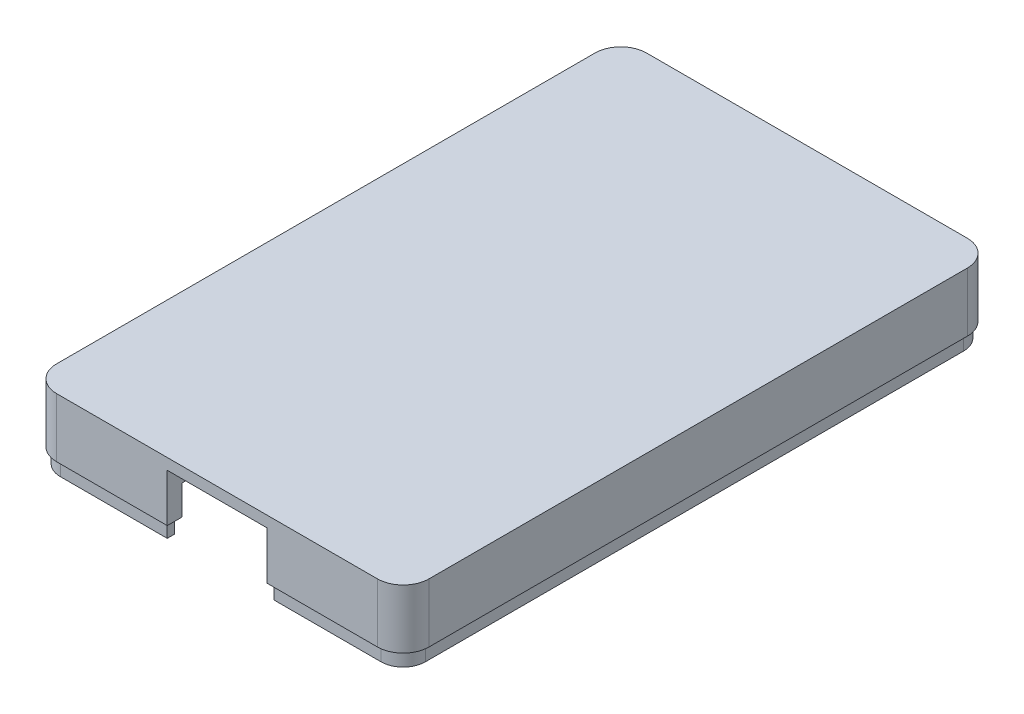
SolidWorks part; units mm, degrees
ref_plane "Alzado" through (0, 0, 0) normal (0, 0, 1) x (1, 0, 0)
ref_plane "Planta" through (0, 0, 0) normal (0, 1, 0) x (1, 0, 0)
ref_plane "Vista lateral" through (0, 0, 0) normal (1, 0, 0) x (0, 0, -1)
sketch "Sketch1" plane through (0, 0, 0) normal (0, 1, 0) x (1, 0, 0)
  line L1 (-21.75, -40) -> (21.75, -40)
  line L2 (-25.25, -36.5) -> (-25.25, 36.5)
  line L3 (-21.75, 40) -> (21.75, 40)
  line L4 (25.25, -36.5) -> (25.25, 36.5)
  line L5 (-25.25, -40) -> (25.25, 40) construction
  line L6 (-25.25, 40) -> (25.25, -40) construction
  arc A0 (-21.75, -40) -> (-25.25, -36.5) centre (-21.75, -36.5) cw
  arc A1 (21.75, -40) -> (25.25, -36.5) centre (21.75, -36.5) ccw
  arc A2 (-25.25, 36.5) -> (-21.75, 40) centre (-21.75, 36.5) cw
  arc A3 (21.75, 40) -> (25.25, 36.5) centre (21.75, 36.5) cw
  point P0 (0, 0)
  dimension "D3" = 3.5
  dimension "D1" = 50.5
  dimension "D2" = 80
extrude "Boss-Extrude1" add sketch "Sketch1" along normal blind 8
sketch "Sketch2" plane through (0, 0, 0) normal (0, -1, 0) x (1, 0, 0)
  line L0 (25.25, 36.5) -> (25.25, -36.5) construction
  line L1 (-19.75, -38) -> (19.75, -38)
  line L2 (-23.25, -34.5) -> (-23.25, 34.5)
  line L3 (-19.75, 38) -> (19.75, 38)
  line L4 (23.25, -34.5) -> (23.25, 34.5)
  line L5 (-23.25, -38) -> (23.25, 38) construction
  line L6 (-23.25, 38) -> (23.25, -38) construction
  line L7 (-21.75, 40) -> (21.75, 40) construction
  arc A0 (19.75, -38) -> (23.25, -34.5) centre (19.75, -34.5) ccw
  arc A1 (-19.75, -38) -> (-23.25, -34.5) centre (-19.75, -34.5) cw
  arc A2 (-23.25, 34.5) -> (-19.75, 38) centre (-19.75, 34.5) cw
  arc A3 (19.75, 38) -> (23.25, 34.5) centre (19.75, 34.5) cw
  point P0 (0, 0)
  dimension "D3" = 3.5
  dimension "D1" = 2
  dimension "D2" = 2
extrude "Cut-Extrude1" cut sketch "Sketch2" against normal blind 4
sketch "Sketch3" plane through (0, 0, 40) normal (0, 0, 1) x (1, 0, 0)
  line L0 (0, 0) -> (0, 8) construction
  line L1 (-21.75, 8) -> (21.75, 8) construction
  line L3 (-6.75, 6.5) -> (6.75, 6.5)
  line L4 (-6.75, 6.5) -> (-6.75, -6.5)
  line L5 (-6.75, -6.5) -> (6.75, -6.5)
  line L6 (6.75, 6.5) -> (6.75, -6.5)
  line L7 (-6.75, 6.5) -> (6.75, -6.5) construction
  line L8 (-6.75, -6.5) -> (6.75, 6.5) construction
  dimension "D1" = 1.5
  dimension "D2" = 13.5
extrude "Cut-Extrude2" cut sketch "Sketch3" against normal blind 15
curve "CurvaComp1"
curve "CurvaComp2"
sketch "Croquis2" plane through (0, 0, 0) normal (0, -1, 0) x (1, 0, 0)
  line L0 (-6.75, 40) -> (-6.75, 38) construction
  line L1 (-6.75, 40) -> (-6.75, 38)
  line L4 (-21.75, 40) -> (-6.75, 40) construction
  line L5 (-25.25, -36.5) -> (-25.25, 36.5) construction
  line L6 (21.75, -40) -> (-21.75, -40) construction
  line L7 (25.25, 36.5) -> (25.25, -36.5) construction
  line L8 (6.75, 40) -> (21.75, 40) construction
  line L9 (-21.75, 40) -> (-6.75, 40)
  line L10 (-25.25, -36.5) -> (-25.25, 36.5)
  line L11 (21.75, -40) -> (-21.75, -40)
  line L12 (25.25, 36.5) -> (25.25, -36.5)
  line L13 (6.75, 40) -> (21.75, 40)
  line L14 (-19.75, 38) -> (-6.75, 38) construction
  line L15 (-23.25, -34.5) -> (-23.25, 34.5) construction
  line L16 (19.75, -38) -> (-19.75, -38) construction
  line L17 (23.25, 34.5) -> (23.25, -34.5) construction
  line L19 (-19.75, 38) -> (-6.75, 38)
  line L20 (-23.25, -34.5) -> (-23.25, 34.5)
  line L21 (19.75, -38) -> (-19.75, -38)
  line L22 (23.25, 34.5) -> (23.25, -34.5)
  line L24 (6.75, 38) -> (6.75, 40) construction
  line L25 (6.75, 38) -> (6.75, 40)
  line L26 (19.75, 38) -> (6.75, 38) construction
  line L27 (19.75, 38) -> (6.75, 38)
  arc A0 (-21.75, 40) -> (-25.25, 36.5) centre (-21.75, 36.5) ccw construction
  arc A1 (-25.25, -36.5) -> (-21.75, -40) centre (-21.75, -36.5) ccw construction
  arc A2 (21.75, -40) -> (25.25, -36.5) centre (21.75, -36.5) ccw construction
  arc A3 (25.25, 36.5) -> (21.75, 40) centre (21.75, 36.5) ccw construction
  arc A4 (-21.75, 40) -> (-25.25, 36.5) centre (-21.75, 36.5) ccw
  arc A5 (-25.25, -36.5) -> (-21.75, -40) centre (-21.75, -36.5) ccw
  arc A6 (21.75, -40) -> (25.25, -36.5) centre (21.75, -36.5) ccw
  arc A7 (25.25, 36.5) -> (21.75, 40) centre (21.75, 36.5) ccw
  arc A8 (-19.75, 38) -> (-23.25, 34.5) centre (-19.75, 34.5) ccw construction
  arc A9 (-23.25, -34.5) -> (-19.75, -38) centre (-19.75, -34.5) ccw construction
  arc A10 (19.75, -38) -> (23.25, -34.5) centre (19.75, -34.5) ccw construction
  arc A11 (23.25, 34.5) -> (19.75, 38) centre (19.75, 34.5) ccw construction
  arc A12 (-19.75, 38) -> (-23.25, 34.5) centre (-19.75, 34.5) ccw
  arc A13 (-23.25, -34.5) -> (-19.75, -38) centre (-19.75, -34.5) ccw
  arc A14 (19.75, -38) -> (23.25, -34.5) centre (19.75, -34.5) ccw
  arc A15 (23.25, 34.5) -> (19.75, 38) centre (19.75, 34.5) ccw
sketch "Croquis3" plane through (0, 0, 0) normal (0, -1, 0) x (1, 0, 0)
  line L12 (7.25, 38.5) -> (19.75, 38.5)
  line L13 (7.25, 38.5) -> (19.75, 38.5)
  line L14 (7.25, 39.5) -> (7.25, 38.5)
  line L15 (7.25, 39.5) -> (7.25, 38.5)
  line L24 (-24.75, 36.5) -> (-24.75, -36.5)
  line L25 (-7.25, 39.5) -> (-21.75, 39.5)
  line L26 (-7.25, 38.5) -> (-7.25, 39.5)
  line L27 (-19.75, 38.5) -> (-7.25, 38.5)
  line L28 (-23.75, -34.5) -> (-23.75, 34.5)
  line L29 (19.75, -38.5) -> (-19.75, -38.5)
  line L30 (23.75, 34.5) -> (23.75, -34.5)
  line L33 (21.75, 39.5) -> (7.25, 39.5)
  line L34 (24.75, -36.5) -> (24.75, 36.5)
  line L35 (-21.75, -39.5) -> (21.75, -39.5)
  line L36 (-24.75, 36.5) -> (-24.75, -36.5)
  line L37 (-7.25, 39.5) -> (-21.75, 39.5)
  line L38 (-7.25, 38.5) -> (-7.25, 39.5)
  line L39 (-19.75, 38.5) -> (-7.25, 38.5)
  line L40 (-23.75, -34.5) -> (-23.75, 34.5)
  line L41 (19.75, -38.5) -> (-19.75, -38.5)
  line L42 (23.75, 34.5) -> (23.75, -34.5)
  line L45 (21.75, 39.5) -> (7.25, 39.5)
  line L46 (24.75, -36.5) -> (24.75, 36.5)
  line L47 (-21.75, -39.5) -> (21.75, -39.5)
  arc A16 (-21.75, 39.5) -> (-24.75, 36.5) centre (-21.75, 36.5) ccw
  arc A17 (-19.75, 38.5) -> (-23.75, 34.5) centre (-19.75, 34.5) ccw
  arc A18 (-23.75, -34.5) -> (-19.75, -38.5) centre (-19.75, -34.5) ccw
  arc A19 (19.75, -38.5) -> (23.75, -34.5) centre (19.75, -34.5) ccw
  arc A20 (23.75, 34.5) -> (19.75, 38.5) centre (19.75, 34.5) ccw
  arc A21 (24.75, 36.5) -> (21.75, 39.5) centre (21.75, 36.5) ccw
  arc A22 (21.75, -39.5) -> (24.75, -36.5) centre (21.75, -36.5) ccw
  arc A23 (-24.75, -36.5) -> (-21.75, -39.5) centre (-21.75, -36.5) ccw
  arc A24 (-21.75, 39.5) -> (-24.75, 36.5) centre (-21.75, 36.5) ccw
  arc A25 (-19.75, 38.5) -> (-23.75, 34.5) centre (-19.75, 34.5) ccw
  arc A26 (-23.75, -34.5) -> (-19.75, -38.5) centre (-19.75, -34.5) ccw
  arc A27 (19.75, -38.5) -> (23.75, -34.5) centre (19.75, -34.5) ccw
  arc A28 (23.75, 34.5) -> (19.75, 38.5) centre (19.75, 34.5) ccw
  arc A29 (24.75, 36.5) -> (21.75, 39.5) centre (21.75, 36.5) ccw
  arc A30 (21.75, -39.5) -> (24.75, -36.5) centre (21.75, -36.5) ccw
  arc A31 (-24.75, -36.5) -> (-21.75, -39.5) centre (-21.75, -36.5) ccw
  dimension "D1" = 0.5
extrude "Saliente-Extruir1" add sketch "Croquis3" along normal blind 2
